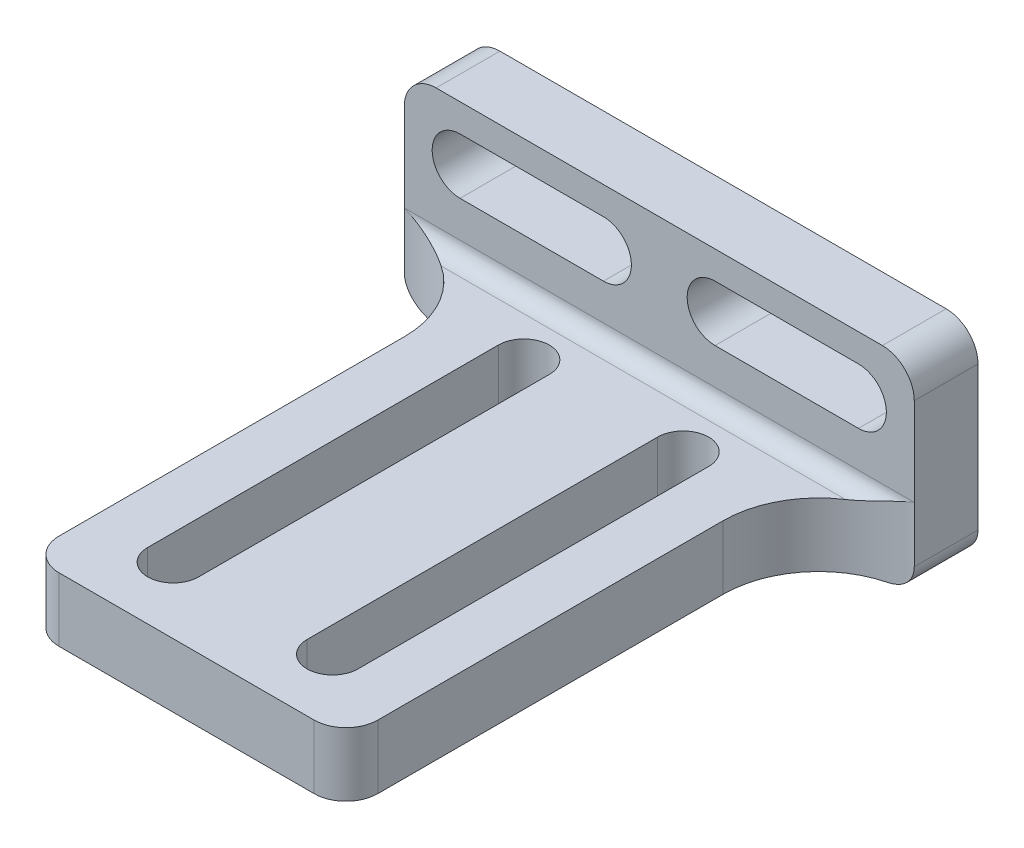
SolidWorks part; units mm, degrees
ref_plane "前视基准面" through (0, 0, 0) normal (0, 0, 1) x (1, 0, 0)
ref_plane "上视基准面" through (0, 0, 0) normal (0, 1, 0) x (1, 0, 0)
ref_plane "右视基准面" through (0, 0, 0) normal (1, 0, 0) x (0, 0, -1)
sketch "草图1" plane through (0, 0, 0) normal (0, 0, 1) x (1, 0, 0)
  line L0 (0, 148.5) -> (0, -94.9538) construction
  line L1 (105, -148.5) -> (-105, -148.5) construction
  line L2 (105, -148.5) -> (105, 148.5) construction
  line L3 (105, 148.5) -> (-105, 148.5) construction
  line L4 (-105, -148.5) -> (-105, 148.5) construction
  line L5 (105, -148.5) -> (-105, 148.5) construction
  line L6 (105, 148.5) -> (-105, -148.5) construction
  line L7 (35.8892, 121.6645) -> (-35.8892, 121.6645)
  line L8 (-35.8892, 121.6645) -> (-66.9017, 102.292)
  line L9 (-75, 40.9339) -> (-75, 31.2613)
  line L10 (-66.9017, 102.292) -> (-66.9017, 52.8701)
  line L11 (75, 40.9339) -> (75, 31.2613)
  line L12 (66.9017, 102.292) -> (66.9017, 52.8701)
  line L13 (35.8892, 121.6645) -> (66.9017, 102.292)
  line L14 (-75, 31.2613) -> (75, 31.2613)
  line L15 (-60, -148.5) -> (-60, -91.8129)
  line L16 (-75, 23.94) -> (75, 23.94)
  line L17 (-75, 23.94) -> (-75, 10.5626)
  line L18 (-38.8455, -105.5906) -> (-66.4608, -113.7617)
  line L19 (-66.4608, -113.7617) -> (-70.1743, -102.7328)
  line L20 (75, 23.94) -> (75, 10.5626)
  line L21 (66.4608, -113.7617) -> (70.1743, -102.7328)
  line L22 (38.8455, -105.5906) -> (66.4608, -113.7617)
  line L23 (-105, 93.0519) -> (105, 93.0519)
  line L24 (-105, 63.0519) -> (105, 63.0519)
  line L25 (-105, -90.0629) -> (-70.5337, -90.0629)
  line L26 (-105, -60.0629) -> (-67.4027, -60.0629)
  line L27 (60, -148.5) -> (60, 148.5)
  line L28 (-60, -58.3129) -> (-45, -58.3129)
  line L29 (-60, -61.8129) -> (-45, -61.8129)
  line L30 (-36, -58.3129) -> (-21, -58.3129)
  line L31 (-36, -61.8129) -> (-21, -61.8129)
  line L32 (-60, -88.3129) -> (-45, -88.3129)
  line L33 (-60, -91.8129) -> (-45, -91.8129)
  line L34 (-36, -88.3129) -> (-21, -88.3129)
  line L35 (-36, -91.8129) -> (-21, -91.8129)
  line L36 (-60, -58.3129) -> (-60, 148.5)
  line L37 (-19.25, -90.0629) -> (105, -90.0629)
  line L38 (-19.25, -60.0629) -> (19.25, -60.0629)
  line L39 (-60, -88.3129) -> (-60, -61.8129)
  line L40 (21, -58.3129) -> (36, -58.3129)
  line L41 (45, -58.3129) -> (60, -58.3129)
  line L42 (60, -61.8129) -> (45, -61.8129)
  line L43 (36, -61.8129) -> (21, -61.8129)
  line L44 (21, -88.3129) -> (36, -88.3129)
  line L45 (21, -91.8129) -> (36, -91.8129)
  line L46 (45, -88.3129) -> (60, -88.3129)
  line L47 (45, -91.8129) -> (60, -91.8129)
  line L48 (37.75, -60.0629) -> (43.25, -60.0629)
  line L49 (58.25, -60.0629) -> (105, -60.0629)
  line L50 (-60, 94.8019) -> (-45, 94.8019)
  line L51 (-36, 94.8019) -> (-21, 94.8019)
  line L52 (-60, 91.3019) -> (-45, 91.3019)
  line L53 (-36, 91.3019) -> (-21, 91.3019)
  line L54 (-60, 64.8019) -> (-45, 64.8019)
  line L55 (-60, 61.3019) -> (-45, 61.3019)
  line L56 (-36, 64.8019) -> (-21, 64.8019)
  line L57 (-36, 61.3019) -> (-21, 61.3019)
  line L58 (21, 94.8019) -> (36, 94.8019)
  line L59 (21, 91.3019) -> (36, 91.3019)
  line L60 (45, 94.8019) -> (60, 94.8019)
  line L61 (45, 91.3019) -> (60, 91.3019)
  line L62 (21, 61.3019) -> (36, 61.3019)
  line L63 (21, 64.8019) -> (36, 64.8019)
  line L64 (45, 61.3019) -> (60, 61.3019)
  line L65 (45, 64.8019) -> (60, 64.8019)
  line L66 (-33.1709, -104.7687) -> (33.1709, -104.7687)
  line L67 (0, -104.7687) -> (0, -148.5) construction
  arc A0 (-75, 40.9339) -> (-66.9017, 52.8701) centre (-79.7474, 52.8701) ccw
  arc A1 (75, 40.9339) -> (66.9017, 52.8701) centre (79.7474, 52.8701) cw
  arc A3 (-60, -88.3129) -> (-60, -91.8129) centre (-60, -90.0629) ccw
  arc A4 (-60, -58.3129) -> (-60, -61.8129) centre (-60, -60.0629) ccw
  circle A5 centre (-60, 63.0519) radius 1.75
  circle A6 centre (-60, 93.0519) radius 1.75
  circle A7 centre (60, 93.0519) radius 1.75
  circle A8 centre (60, 63.0519) radius 1.75
  arc A9 (60, -91.8129) -> (60, -88.3129) centre (60, -90.0629) ccw
  arc A10 (60, -61.8129) -> (60, -58.3129) centre (60, -60.0629) ccw
  arc A11 (-36, -58.3129) -> (-36, -61.8129) centre (-36, -60.0629) ccw
  arc A12 (-36, -88.3129) -> (-36, -91.8129) centre (-36, -90.0629) ccw
  arc A13 (36, -61.8129) -> (36, -58.3129) centre (36, -60.0629) ccw
  arc A14 (36, -91.8129) -> (36, -88.3129) centre (36, -90.0629) ccw
  arc A15 (-45, -61.8129) -> (-45, -58.3129) centre (-45, -60.0629) ccw
  arc A16 (-21, -61.8129) -> (-21, -58.3129) centre (-21, -60.0629) ccw
  arc A17 (-45, -91.8129) -> (-45, -88.3129) centre (-45, -90.0629) ccw
  arc A18 (-21, -91.8129) -> (-21, -88.3129) centre (-21, -90.0629) ccw
  arc A19 (45, -58.3129) -> (45, -61.8129) centre (45, -60.0629) ccw
  arc A20 (21, -58.3129) -> (21, -61.8129) centre (21, -60.0629) ccw
  arc A21 (21, -88.3129) -> (21, -91.8129) centre (21, -90.0629) ccw
  arc A22 (45, -88.3129) -> (45, -91.8129) centre (45, -90.0629) ccw
  circle A23 centre (-36, 93.0519) radius 1.75
  circle A24 centre (-36, 63.0519) radius 1.75
  circle A25 centre (36, 93.0519) radius 1.75
  circle A26 centre (36, 63.0519) radius 1.75
  circle A27 centre (-45, 93.0519) radius 1.75
  circle A28 centre (-21, 93.0519) radius 1.75
  circle A29 centre (-45, 63.0519) radius 1.75
  circle A30 centre (-21, 63.0519) radius 1.75
  circle A31 centre (21, 93.0519) radius 1.75
  circle A32 centre (21, 63.0519) radius 1.75
  circle A33 centre (45, 93.0519) radius 1.75
  circle A34 centre (45, 63.0519) radius 1.75
  arc A35 (33.1709, -104.7687) -> (38.8455, -105.5906) centre (33.1709, -124.7687) cw
  arc A36 (-33.1709, -104.7687) -> (-38.8455, -105.5906) centre (-33.1709, -124.7687) ccw
  spline S0 degree 3 poles (-75, 10.5626) (-72.6959, 1.9073) (-70.3396, -13.3728) (-67.1028, -43.6255) (-66.7657, -72.9327) (-71.8903, -95.1489) (-70.1743, -102.7328) knots 0 0 0 0 0.235247 0.406294 0.801186 1 1 1 1
  spline S1 degree 3 poles (75, 10.5626) (72.6959, 1.9073) (70.3396, -13.3728) (67.1028, -43.6255) (66.7657, -72.9327) (71.8903, -95.1489) (70.1743, -102.7328) knots 0 0 0 0 0.235247 0.406294 0.801186 1 1 1 1
  point P0 (0, 0)
  point P27 (0, 121.6645)
  point P42 (0, -94.0966)
  dimension "D1" = 60
  dimension "D4" = 20
  dimension "D5" = 24
  dimension "D7" = 24
  dimension "D9" = 15
  dimension "D10" = 15
  dimension "D13" = 24
  dimension "D17" = 15
  dimension "D2" = 30
  dimension "D3" = 30
  dimension "D6" = 24
  dimension "D8" = 24
  dimension "D11" = 15
  dimension "D12" = 15
  dimension "D14" = 24
  dimension "D15" = 24
  dimension "D16" = 24
  dimension "D18" = 15
  dimension "D19" = 15
  dimension "D20" = 15
  dimension "D21" = 15
  dimension "D22" = 15
  dimension "D23" = 15
  dimension "D24" = 15
  dimension "D25" = 15
  dimension "D26" = 15
  dimension "D27" = 15
  dimension "D28" = 15
  dimension "D29" = 3.5
  dimension "D30" = 3.5
  dimension "D31" = 3.5
extrude "凸台-拉伸1" add sketch "草图1" along normal blind 3 contours A34 L24 A26 L62 A32 A30 L57 A24 A29 L55 L36 L14 L27 L64 | A5 L24 L10 A0 L9 L14 L36 | A6 L23 L10 L24 A5 L36 | A6 L36 L8 L10 L23 | A33 L60 L27 L13 L7 L8 L36 L50 A27 L23 A23 L51 A28 A31 L58 A25 | A34 L65 L27 L61 A33 L23 A25 L59 A31 A28 L53 A23 A27 L52 L36 L54 A29 L24 A24 L56 A30 A32 L63 A26 | A7 L23 L12 L13 L27 | A8 L24 L12 L23 A7 L27 | A8 L27 L14 L11 A1 L12 L24 | A22 L46 L27 L42 A19 A13 L43 A20 A16 L31 A11 L30 L40 L41 L16 L36 L28 A15 L29 L39 L32 A17 L33 L15 L18 L22 L47 A14 L45 A21 A18 L35 A12 L34 | L17 S0 L19 L18 L15 A3 L39 A4 L36 L16 | S1 L20 L16 L27 A10 L49 | S1 L49 A10 L27 A9 L37 | S1 L37 A9 L27 L22 L21 region at (0, 106.7597, 0) region at (63.3118, 98.9762, 0) region at (-63.3118, 98.9762, 0) region at (63.5153, 78.0519, 0) region at (-63.5153, 78.0519, 0) region at (65.7633, 44.067, 0) region at (0, 78.0519, 0) region at (-65.7633, 44.067, 0) region at (0, 46.6707, 0) region at (0, -40.0712, 0) region at (65.6849, -11.6712, 0) region at (-65.3451, -38.0027, 0) region at (64.4303, -76.0355, 0) region at (65.0264, -100.7629, 0)
sketch "草图7" plane through (0, 0, 0) normal (0, 0, -1) x (-1, 0, 0)
  line L0 (0, 121.6645) -> (0, -104.7687) construction
  line L1 (-35.8892, 121.6645) -> (35.8892, 121.6645) construction
  line L2 (33.1709, -104.7687) -> (-33.1709, -104.7687) construction
  line L3 (0, 41.2613) -> (-21, 41.2613) construction
  line L4 (0, 41.2613) -> (21, 41.2613) construction
  line L5 (0, 13.94) -> (-21, 13.94) construction
  line L6 (0, 13.94) -> (21, 13.94) construction
  line L7 (75, 23.94) -> (-75, 23.94) construction
  line L8 (75, 31.2613) -> (-75, 31.2613) construction
  circle A0 centre (-21, 41.2613) radius 2.25
  circle A1 centre (21, 41.2613) radius 2.25
  circle A2 centre (-21, 13.94) radius 2.25
  circle A3 centre (21, 13.94) radius 2.25
  dimension "D1" = 10
  dimension "D2" = 10
extrude "切除-拉伸2" cut sketch "草图7" against normal through all
sketch "草图8" plane through (0, 0, 3) normal (0, 0, 1) x (1, 0, 0)
  line L0 (0, 121.6645) -> (0, -1.9696) construction
  line L1 (35.8892, 121.6645) -> (-35.8892, 121.6645) construction
  line L2 (-33.1709, -104.7687) -> (33.1709, -104.7687) construction
  line L3 (-33.409, 20.409) -> (-12.6214, -0.3786)
  line L4 (31.818, -51.182) -> (-31.818, -51.182)
  line L5 (35, -48) -> (35, 15.6418)
  line L8 (-35, 18.818) -> (-12.6214, -3.5605) construction
  line L9 (-33.409, -52.773) -> (-12.5737, -31.9377)
  line L10 (-36.591, 17.227) -> (-15.8034, -3.5605)
  line L11 (33.4105, 20.4105) -> (12.573, -0.427)
  line L12 (15.803, -3.5609) -> (36.5881, 17.2241)
  line L13 (31.8195, 18.8195) -> (-31.818, 18.818)
  line L14 (-15.8038, -28.8038) -> (-36.591, -49.591)
  line L15 (12.5534, -31.9174) -> (33.409, -52.773)
  line L16 (34.9993, 18.8173) -> (12.6207, -3.5613) construction
  line L17 (0, -30.3951) -> (0, -104.7687) construction
  line L18 (-35, -48) -> (-35, 15.636)
  line L19 (-11.9624, -1.9696) -> (-14.2124, -1.9696) construction
  line L20 (15.8034, -28.8034) -> (36.591, -49.591)
  line L21 (14.2117, -30.3951) -> (11.9607, -30.3951) construction
  line L22 (14.2117, -30.3951) -> (14.2117, -28.1441) construction
  line L23 (14.2117, -1.9696) -> (11.9612, -1.9696) construction
  line L24 (-14.2124, -30.3951) -> (-14.2124, -28.1446) construction
  line L25 (14.2117, -30.3951) -> (12.62, -28.8034) construction
  line L26 (14.2117, -1.9696) -> (12.6204, -3.5609) construction
  line L27 (12.6207, -28.8027) -> (35, -51.182) construction
  line L28 (-12.6215, -3.5606) -> (-14.2124, -1.9696) construction
  line L29 (-14.2124, -4.2196) -> (-14.2124, -1.9696) construction
  line L30 (-12.6214, -28.8034) -> (-35, -51.182) construction
  line L31 (-12.6211, -28.8037) -> (-14.2124, -30.3951) construction
  line L32 (-11.9619, -30.3951) -> (-14.2124, -30.3951) construction
  line L33 (14.2117, -4.2201) -> (14.2117, -1.9696) construction
  line L34 (11.0312, -30.3951) -> (0, -30.3951) construction
  arc A0 (-33.409, 20.409) -> (-36.591, 17.227) centre (-35, 18.818) ccw
  arc A1 (36.5881, 17.2241) -> (33.4105, 20.4105) centre (34.9993, 18.8173) ccw
  arc A2 (-36.591, -49.591) -> (-33.409, -52.773) centre (-35, -51.182) ccw
  arc A3 (33.409, -52.773) -> (36.591, -49.591) centre (35, -51.182) ccw
  arc A4 (-15.8034, -3.5605) -> (-12.6214, -0.3786) centre (-14.2124, -1.9696) ccw
  arc A5 (12.6692, -0.3308) -> (15.803, -3.5609) centre (14.2117, -1.9696) ccw
  arc A6 (-12.6699, -32.0338) -> (-15.8038, -28.8038) centre (-14.2124, -30.3951) ccw
  arc A7 (15.8034, -28.8034) -> (12.6894, -32.0534) centre (14.2117, -30.3951) ccw
  circle A8 centre (-0.0004, -16.1823) radius 8
  point P6 (0, -16.182)
  point P13 (-0.0004, -16.1823)
extrude "切除-拉伸3" cut sketch "草图8" against normal through all contours L10 A4 L3 A0 | L11 A5 L12 A1 | L20 A7 L15 A3 | L9 A6 L14 A2 | A8 region at (-24.6062, 8.4242, 3) region at (24.6054, 8.4234, 3) region at (-24.6061, -40.7881, 3) region at (24.6056, -40.7877, 3) region at (-0.0004, -16.1823, 3)
sketch "草图9" plane through (0, 0, 3) normal (0, 0, 1) x (1, 0, 0)
  line L0 (-70.7828, -98.747) -> (70.7828, -98.747) construction
  line L1 (0, -98.747) -> (0, -104.7687) construction
  line L2 (55, -100.497) -> (20, -100.497)
  line L3 (-55, -96.997) -> (-20, -96.997)
  line L4 (-55, -100.497) -> (-20, -100.497)
  line L5 (-33.1709, -104.7687) -> (33.1709, -104.7687) construction
  line L6 (55, -96.997) -> (20, -96.997)
  arc A0 (-55, -96.997) -> (-55, -100.497) centre (-55, -98.747) ccw
  arc A1 (-20, -100.497) -> (-20, -96.997) centre (-20, -98.747) ccw
  arc A2 (20, -100.497) -> (20, -96.997) centre (20, -98.747) cw
  arc A3 (55, -96.997) -> (55, -100.497) centre (55, -98.747) cw
  spline S0 degree 3 poles (-75, 10.5626) (-72.6959, 1.9073) (-70.3396, -13.3728) (-67.1028, -43.6255) (-66.7657, -72.9327) (-71.8903, -95.1489) (-70.1743, -102.7328) knots 0 0 0 0 0.235247 0.406294 0.801186 1 1 1 1 construction
  spline S1 degree 3 poles (75, 10.5626) (72.6959, 1.9073) (70.3396, -13.3728) (67.1028, -43.6255) (66.7657, -72.9327) (71.8903, -95.1489) (70.1743, -102.7328) knots 0 0 0 0 0.235247 0.406294 0.801186 1 1 1 1 construction
  dimension "D1" = 35
  dimension "D2" = 20
extrude "切除-拉伸4" cut sketch "草图9" against normal blind 3
sketch "草图10" plane through (0, 0, 3) normal (0, 0, 1) x (1, 0, 0)
  line L0 (-21, -60.0629) -> (-21, -90.0629) construction
  line L1 (21, -60.0629) -> (21, -90.0629) construction
  line L2 (-21, -75.0629) -> (-17.5, -75.0629) construction
  line L4 (12.5, -80.0629) -> (-12.5, -80.0629)
  line L6 (12.5, -70.0629) -> (-12.5, -70.0629)
  line L11 (17.5, -75.0629) -> (21, -75.0629) construction
  arc A0 (-12.5, -70.0629) -> (-12.5, -80.0629) centre (-12.5, -75.0629) ccw
  arc A1 (12.5, -80.0629) -> (12.5, -70.0629) centre (12.5, -75.0629) ccw
  point P11 (0, -75.0629)
extrude "切除-拉伸5" cut sketch "草图10" against normal blind 3
sketch "草图11" plane through (0, 0, 3) normal (0, 0, 1) x (1, 0, 0)
  line L0 (-21, 93.0519) -> (-21, 63.0519) construction
  line L1 (21, 93.0519) -> (21, 63.0519) construction
  line L2 (-21, 78.0519) -> (-20, 78.0519) construction
  line L4 (15, 73.0519) -> (-15, 73.0519)
  line L6 (15, 83.0519) -> (-15, 83.0519)
  line L10 (20, 78.0519) -> (21, 78.0519) construction
  arc A0 (-15, 83.0519) -> (-15, 73.0519) centre (-15, 78.0519) ccw
  arc A1 (15, 73.0519) -> (15, 83.0519) centre (15, 78.0519) ccw
  point P10 (0, 78.0519)
  dimension "D1" = 30
extrude "切除-拉伸8" cut sketch "草图11" against normal blind 3
sketch "草图12" plane through (0, 0, 3) normal (0, 0, 1) x (1, 0, 0)
  line L0 (0, 121.6645) -> (0, 83.0519) construction
  line L1 (35.8892, 121.6645) -> (-35.8892, 121.6645) construction
  line L2 (15, 83.0519) -> (-15, 83.0519) construction
  circle A0 centre (0, 106.3718) radius 11 construction
  circle A1 centre (0, 106.3718) radius 8 construction
  circle A2 centre (0, 114.3718) radius 1.7
  circle A3 centre (0, 98.3718) radius 1.7
  circle A4 centre (8, 106.3718) radius 1.7
  circle A5 centre (-8, 106.3718) radius 1.7
extrude "切除-拉伸9" cut sketch "草图12" against normal blind 3
sketch "草图13" plane through (0, 0, 3) normal (0, 0, 1) x (1, 0, 0)
  line L0 (0, -104.7687) -> (0, -80.0629) construction
  line L1 (-33.1709, -104.7687) -> (33.1709, -104.7687) construction
  line L2 (-12.5, -80.0629) -> (12.5, -80.0629) construction
  circle A0 centre (0, -92.4158) radius 8 construction
  circle A1 centre (0, -84.4158) radius 1.7
  circle A2 centre (8, -92.4158) radius 1.7
  circle A3 centre (0, -100.4158) radius 1.7
  circle A4 centre (-8, -92.4158) radius 1.7
extrude "切除-拉伸11" cut sketch "草图13" against normal blind 3
sketch "草图14" plane through (0, 0, 3) normal (0, 0, 1) x (1, 0, 0)
  line L0 (0, 23.94) -> (0, -104.7687) construction
  line L1 (-55.4755, 8.9197) -> (-55.4755, -46.0803)
  line L2 (-58.9755, 8.9197) -> (-58.9755, -46.0803)
  line L3 (-75, 23.94) -> (75, 23.94) construction
  line L4 (-33.1709, -104.7687) -> (33.1709, -104.7687) construction
  line L5 (58.9755, 8.9197) -> (58.9755, -46.0803)
  line L6 (55.4755, 8.9197) -> (55.4755, -46.0803)
  arc A0 (-55.4755, 8.9197) -> (-58.9755, 8.9197) centre (-57.2255, 8.9197) ccw
  arc A1 (-58.9755, -46.0803) -> (-55.4755, -46.0803) centre (-57.2255, -46.0803) ccw
  arc A2 (58.9755, -46.0803) -> (55.4755, -46.0803) centre (57.2255, -46.0803) cw
  arc A3 (55.4755, 8.9197) -> (58.9755, 8.9197) centre (57.2255, 8.9197) cw
extrude "切除-拉伸12" cut sketch "草图14" against normal through all
fillet "圆角1" radius 2 2 edges at (75, 31.2613, 1.5) (-75, 31.2613, 1.5)
fillet "圆角2" radius 2 2 edges at (-75, 23.94, 1.5) (75, 23.94, 1.5)
sketch "草图15" plane through (0, 0, 0) normal (0, 0, -1) x (-1, 0, 0)
  line L0 (0, 121.6645) -> (0, 31.2613) construction
  line L1 (-35.8892, 121.6645) -> (35.8892, 121.6645) construction
  line L2 (73, 31.2613) -> (-73, 31.2613) construction
  line L3 (-27.5188, 121.6645) -> (-63.6963, 99.0657) construction
  line L4 (-35.8892, 121.6645) -> (-66.9017, 102.292) construction
  line L5 (-61.1842, 102.4035) -> (-34.7748, 118.9006)
  line L6 (-59.5948, 99.8591) -> (-33.1854, 116.3562)
  line L7 (27.5188, 121.6645) -> (63.6963, 99.0657) construction
  line L8 (59.5948, 99.8591) -> (33.1854, 116.3562)
  line L9 (61.1842, 102.4035) -> (34.7748, 118.9006)
  arc A0 (-61.1842, 102.4035) -> (-59.5948, 99.8591) centre (-60.3895, 101.1313) ccw
  arc A1 (-33.1854, 116.3562) -> (-34.7748, 118.9006) centre (-33.9801, 117.6284) ccw
  arc A2 (33.1854, 116.3562) -> (34.7748, 118.9006) centre (33.9801, 117.6284) cw
  arc A3 (61.1842, 102.4035) -> (59.5948, 99.8591) centre (60.3895, 101.1313) cw
extrude "切除-拉伸13" cut sketch "草图15" against normal through all
sketch "草图16" plane through (0, 0, 0) normal (0, 0, -1) x (-1, 0, 0)
  line L0 (0, 121.6645) -> (0, 31.2613) construction
  line L1 (-35.8892, 121.6645) -> (35.8892, 121.6645) construction
  line L2 (73, 31.2613) -> (-73, 31.2613) construction
  line L3 (-21, 41.2613) -> (-66.71, 41.2613) construction
  line L4 (-61.517, 42.7613) -> (-32.0563, 42.7613)
  line L5 (-61.517, 39.7613) -> (-32.0563, 39.7613)
  line L6 (21, 41.2613) -> (66.71, 41.2613) construction
  line L7 (61.517, 39.7613) -> (32.0563, 39.7613)
  line L8 (61.517, 42.7613) -> (32.0563, 42.7613)
  arc A0 (-61.517, 42.7613) -> (-61.517, 39.7613) centre (-61.517, 41.2613) ccw
  arc A1 (-32.0563, 39.7613) -> (-32.0563, 42.7613) centre (-32.0563, 41.2613) ccw
  arc A2 (32.0563, 39.7613) -> (32.0563, 42.7613) centre (32.0563, 41.2613) cw
  arc A3 (61.517, 42.7613) -> (61.517, 39.7613) centre (61.517, 41.2613) cw
extrude "切除-拉伸14" cut sketch "草图16" against normal through all
sketch "草图17" plane through (0, 0, 0) normal (0, 0, -1) x (-1, 0, 0)
  text T0 "Y" font "黑体" height in points 72
extrude "切除-拉伸15" cut sketch "草图17" against normal through all
sketch "草图18" plane through (0, 0, 0) normal (0, 0, -1) x (-1, 0, 0)
  text T0 "H" font "黑体" height in points 72
extrude "切除-拉伸16" cut sketch "草图18" against normal through all
ref_plane "基准面1" through (0, 0, 13) normal (0, 0, 1) x (1, 0, 0)
sketch "草图19" plane through (0, 0, 13) normal (0, 0, 1) x (1, 0, 0)
  line L2 (20, -100.497) -> (55, -100.497) construction
  line L3 (55, -96.997) -> (20, -96.997) construction
  line L6 (20, -100.497) -> (45, -100.497)
  line L7 (45, -96.997) -> (20, -96.997)
  line L8 (0, -100.4158) -> (0, -70.0629) construction
  line L9 (12.5, -70.0629) -> (-12.5, -70.0629) construction
  line L10 (45, -98.747) -> (20, -98.747) construction
  line L11 (-16.5, -96.247) -> (-43.7, -100.497) construction
  line L12 (16.5, -101.247) -> (16.5, -104.7687) construction
  line L14 (16.5, -101.247) -> (16.5, -96.247)
  line L15 (16.5, -96.247) -> (48.5, -96.247)
  line L16 (48.5, -101.247) -> (48.5, -96.247)
  line L17 (16.5, -101.247) -> (48.5, -96.247) construction
  line L18 (16.5, -96.247) -> (43.7, -100.497) construction
  line L19 (-33.1709, -104.7687) -> (33.1709, -104.7687) construction
  line L21 (48.5, -101.247) -> (48.5, -104.7687)
  line L22 (48.5, -104.7687) -> (16.5, -104.7687)
  line L23 (16.5, -101.247) -> (16.5, -104.7687)
  line L24 (-16.5, -101.247) -> (-48.5, -96.247) construction
  line L25 (-16.5, -101.247) -> (-16.5, -104.7687) construction
  line L26 (-45, -98.747) -> (-20, -98.747) construction
  line L27 (-16.5, -101.247) -> (-16.5, -104.7687)
  line L28 (-48.5, -104.7687) -> (-16.5, -104.7687)
  line L29 (-48.5, -101.247) -> (-48.5, -104.7687)
  line L30 (-48.5, -101.247) -> (-48.5, -96.247)
  line L31 (-16.5, -96.247) -> (-48.5, -96.247)
  line L32 (-16.5, -101.247) -> (-16.5, -96.247)
  line L33 (-45, -96.997) -> (-20, -96.997)
  line L34 (-20, -100.497) -> (-45, -100.497)
  arc A0 (-45, -100.497) -> (-45, -96.997) centre (-45, -98.747) cw
  arc A2 (20, -96.997) -> (20, -100.497) centre (20, -98.747) ccw construction
  arc A3 (-20, -96.997) -> (-20, -100.497) centre (-20, -98.747) cw
  arc A6 (20, -96.997) -> (20, -100.497) centre (20, -98.747) ccw
  arc A8 (45, -100.497) -> (45, -96.997) centre (45, -98.747) ccw
  point P2 (32.5, -98.747)
  point P36 (-32.5, -98.747)
extrude "凸台-拉伸2" add sketch "草图19" along normal blind 4 separate body
sketch "草图21" plane through (0, 0, 17) normal (0, 0, 1) x (1, 0, 0)
  line L0 (-46.75, -98.747) -> (-18.25, -98.747) construction
  line L1 (-32.5, -96.997) -> (-32.5, -100.497) construction
  line L2 (-20, -96.997) -> (-45, -96.997) construction
  line L3 (-45, -100.497) -> (-20, -100.497) construction
  line L4 (-36, -96.997) -> (-29, -96.997)
  line L5 (-36, -100.497) -> (-29, -100.497)
  line L6 (0, -104.7687) -> (0, -70.0629) construction
  line L7 (-33.1709, -104.7687) -> (33.1709, -104.7687) construction
  line L8 (12.5, -70.0629) -> (-12.5, -70.0629) construction
  line L9 (32.5, -96.997) -> (32.5, -100.497) construction
  line L10 (36, -100.497) -> (29, -100.497)
  line L11 (36, -96.997) -> (29, -96.997)
  arc A0 (-45, -96.997) -> (-45, -100.497) centre (-45, -98.747) ccw construction
  arc A1 (-20, -100.497) -> (-20, -96.997) centre (-20, -98.747) ccw construction
  arc A2 (-36, -100.497) -> (-36, -96.997) centre (-36, -98.747) ccw
  arc A3 (-29, -96.997) -> (-29, -100.497) centre (-29, -98.747) ccw
  arc A4 (29, -96.997) -> (29, -100.497) centre (29, -98.747) cw
  arc A5 (36, -100.497) -> (36, -96.997) centre (36, -98.747) cw
  point P18 (-32.5, -98.747)
  dimension "D1" = 3.5
  dimension "D2" = 3.5
extrude "凸台-拉伸4" add sketch "草图21" against normal up to surface (4 mm away) up to face at (32.5, -100.5079, 13)
sketch "草图23" plane through (0, 0, 13) normal (0, 0, 1) x (1, 0, 0)
  line L0 (-16.5, -104.7687) -> (-16.5, -120.6552) construction
  line L1 (48.5, -104.7687) -> (48.5, -120.6552) construction
  line L2 (-16.5, -104.7687) -> (-16.5, -96.247) construction
  line L4 (-48.5, -104.7687) -> (-48.5, -107.7687)
  line L5 (-48.5, -107.7687) -> (-16.5, -107.7687)
  line L6 (-16.5, -104.7687) -> (-16.5, -107.7687)
  line L8 (16.5, -104.7687) -> (16.5, -107.7687)
  line L9 (16.5, -107.7687) -> (48.5, -107.7687)
  line L10 (48.5, -104.7687) -> (48.5, -107.7687)
  line L12 (-48.5, -104.7687) -> (-48.5, -102.7687)
  line L13 (-48.5, -102.7687) -> (-16.5, -102.7687)
  line L14 (-16.5, -104.7687) -> (-16.5, -102.7687)
  line L17 (16.5, -104.7687) -> (16.5, -102.7687)
  line L18 (16.5, -102.7687) -> (48.5, -102.7687)
  line L19 (48.5, -104.7687) -> (48.5, -102.7687)
extrude "凸台-拉伸5" add sketch "草图23" along normal blind 35
sketch "草图25" plane through (0, -102.7687, 0) normal (0, 1, 0) x (1, 0, 0)
  line L0 (-32.5, -17) -> (-32.5, -48) construction
  line L1 (-16.5, -17) -> (-48.5, -17) construction
  line L2 (-16.5, -48) -> (-48.5, -48) construction
  line L3 (-22.5, -17) -> (-22.5, -48)
  line L4 (-48.5, -17) -> (-42.5, -17)
  line L5 (-48.5, -17) -> (-48.5, -48)
  line L6 (-48.5, -48) -> (-42.5, -48)
  line L7 (-42.5, -17) -> (-42.5, -48)
  line L8 (-16.5, -17) -> (-16.5, -48)
  line L9 (-16.5, -17) -> (-22.5, -17)
  line L10 (-16.5, -48) -> (-22.5, -48)
  line L11 (0, 0) -> (0, -48) construction
  line L12 (32.5, -17) -> (32.5, -48) construction
  line L13 (16.5, -48) -> (22.5, -48)
  line L14 (16.5, -17) -> (22.5, -17)
  line L15 (16.5, -17) -> (16.5, -48)
  line L16 (42.5, -17) -> (42.5, -48)
  line L17 (48.5, -48) -> (42.5, -48)
  line L18 (48.5, -17) -> (48.5, -48)
  line L19 (48.5, -17) -> (42.5, -17)
  line L20 (22.5, -17) -> (22.5, -48)
extrude "切除-拉伸17" cut sketch "草图25" against normal up to surface (5 mm away) up to face at (-32.5, -107.7687, 30.5)
fillet "圆角3" radius 6 2 edges at (22.5, -105.2687, 17) (42.5, -105.2687, 17)
fillet "圆角4" radius 6 2 edges at (-42.5, -105.2687, 17) (-22.5, -105.2687, 17)
fillet "圆角5" radius 1.5 4 edges at (48.5, -107.7687, 15) (16.5, -107.7687, 15) (16.5, -96.247, 15) (48.5, -96.247, 15)
fillet "圆角6" radius 1.5 4 edges at (-48.5, -107.7687, 15) (-48.5, -96.247, 15) (-16.5, -96.247, 15) (-16.5, -107.7687, 15)
sketch "草图26" plane through (0, -107.7687, 0) normal (0, -1, 0) x (1, 0, 0)
  line L0 (0, 0) -> (0, 51.2514) construction
  line L2 (22.5, 48) -> (42.5, 48) construction
  line L4 (42.5, 48) -> (32.5, 48) construction
  line L6 (75.7359, 13) -> (-75.7359, 13) construction
  line L7 (37.5, 20.5) -> (37.5, 13) construction
  line L9 (35.9, 20.5) -> (35.9, 32.5)
  line L11 (39.1, 20.5) -> (39.1, 32.5)
  line L12 (27.5, 30.9) -> (27.5, 22.1) construction
  line L13 (25.9, 20.5) -> (25.9, 32.5)
  line L14 (37.5, 30.9) -> (37.5, 22.1) construction
  line L15 (29.1, 20.5) -> (29.1, 32.5)
  line L16 (-37.5, 34.1) -> (-37.5, 22.1) construction
  line L17 (-27.5, 34.1) -> (-27.5, 22.1) construction
  line L18 (-29.1, 20.5) -> (-29.1, 32.5)
  line L19 (-25.9, 20.5) -> (-25.9, 32.5)
  line L20 (-39.1, 20.5) -> (-39.1, 32.5)
  line L21 (-35.9, 20.5) -> (-35.9, 32.5)
  arc A1 (35.9, 20.5) -> (39.1, 20.5) centre (37.5, 20.5) ccw
  arc A2 (29.1, 20.5) -> (25.9, 20.5) centre (27.5, 20.5) cw
  arc A5 (-29.1, 20.5) -> (-25.9, 20.5) centre (-27.5, 20.5) ccw
  arc A6 (-35.9, 20.5) -> (-39.1, 20.5) centre (-37.5, 20.5) cw
  arc A8 (39.1, 32.5) -> (35.9, 32.5) centre (37.5, 32.5) ccw
  arc A9 (29.1, 32.5) -> (25.9, 32.5) centre (27.5, 32.5) ccw
  arc A10 (-29.1, 32.5) -> (-25.9, 32.5) centre (-27.5, 32.5) cw
  arc A11 (-39.1, 32.5) -> (-35.9, 32.5) centre (-37.5, 32.5) cw
  point P15 (37.5, 30.5)
  point P32 (27.5, 30.5)
  point P49 (-27.5, 30.5)
  point P50 (-37.5, 30.5)
  dimension "D1" = 12
extrude "切除-拉伸18" cut sketch "草图26" against normal blind 5
sketch "草图27" plane through (42.5, 0, 0) normal (1, 0, 0) x (0, 0, -1)
  line L0 (-17, -106.2687) -> (-17, -102.7687) construction
  line L1 (-48, -102.7687) -> (-17, -102.7687)
  line L2 (-48, -102.7687) -> (-48, -103.7687)
  line L3 (-48, -103.7687) -> (-17, -103.7687)
  line L4 (-17, -102.7687) -> (-17, -103.7687)
extrude "切除-拉伸19" cut sketch "草图27" against normal blind 95 and the other way blind 15
fillet "圆角8" radius 1 1 edges at (-32.5, -103.7687, 17)
fillet "圆角9" radius 1 1 edges at (32.5, -103.7687, 17)
fillet "圆角10" radius 3 2 edges at (-22.5, -105.7687, 48) (-42.5, -105.7687, 48)
sketch "草图28" plane through (0, -107.7687, 0) normal (0, -1, 0) x (1, 0, 0)
  line L0 (-42.5, 23) -> (-42.5, 45) construction
  line L1 (42.5, 48) -> (-42.5, 48)
  line L2 (42.5, 48) -> (42.5, 37.6569)
  line L3 (42.5, 37.6569) -> (-42.5, 37.6569)
  line L4 (-42.5, 48) -> (-42.5, 37.6569)
extrude "切除-拉伸20" cut sketch "草图28" against normal blind 5
fillet "圆角12" radius 3 2 edges at (22.5, -105.7687, 37.6569) (42.5, -105.7687, 37.6569)
fillet "圆角13" radius 3 2 edges at (-42.5, -105.7687, 37.6569) (-22.5, -105.7687, 37.6569)
ref_plane "基准面2" through (0, -112.7687, 0) normal (0, -1, 0) x (-1, 0, 0)
sketch "草图31" plane through (0, 121.6645, 0) normal (0, 1, 0) x (1, 0, 0)
  line L1 (-79.0565, 2.2725) -> (80.5534, 2.2725)
  line L2 (-79.0565, 2.2725) -> (-79.0565, -7.1241)
  line L3 (-79.0565, -7.1241) -> (80.5534, -7.1241)
  line L4 (80.5534, 2.2725) -> (80.5534, -7.1241)
extrude "切除-拉伸21" cut sketch "草图31" against normal blind 265
sketch "草图32" plane through (0, 0, 13) normal (0, 0, -1) x (-1, 0, 0)
  line L0 (-16.5, -102.0079) -> (-16.5, -88.4862) construction
  line L1 (-16.5, -97.747) -> (-16.5, -106.2687) construction
  line L2 (48.5, -102.0079) -> (48.5, -85.1941) construction
  line L3 (48.5, -97.747) -> (48.5, -106.2687) construction
  line L4 (-48.5, -97.747) -> (-48.5, -87.7348) construction
  line L5 (16.5, -97.747) -> (16.5, -85.1941) construction
  line L6 (-29, -96.997) -> (-20, -96.997) construction
  line L7 (-48.5, -97.747) -> (-46.4361, -97.747)
  line L8 (-48.5, -97.747) -> (-48.5, -95.247)
  line L9 (-48.5, -95.247) -> (-16.5, -95.247)
  line L10 (-16.5, -97.747) -> (-16.5, -95.247)
  line L11 (-45, -96.997) -> (-36, -96.997) construction
  line L12 (-29, -96.997) -> (-20, -96.997)
  line L13 (-45, -96.997) -> (-36, -96.997)
  line L14 (-34.5639, -97.747) -> (-30.4361, -97.747)
  line L15 (-18.5639, -97.747) -> (-16.5, -97.747)
  line L16 (-16.5, -102.0079) -> (16.5, -102.0079) construction
  line L17 (16.5, -106.2687) -> (16.5, -97.747) construction
  line L18 (0, -102.0079) -> (0, -80.5827) construction
  line L19 (18.5639, -97.747) -> (16.5, -97.747)
  line L20 (34.5639, -97.747) -> (30.4361, -97.747)
  line L21 (45, -96.997) -> (36, -96.997)
  line L22 (29, -96.997) -> (20, -96.997)
  line L23 (16.5, -97.747) -> (16.5, -95.247)
  line L24 (48.5, -95.247) -> (16.5, -95.247)
  line L25 (48.5, -97.747) -> (48.5, -95.247)
  line L26 (48.5, -97.747) -> (46.4361, -97.747)
  arc A0 (-20, -100.497) -> (-20, -96.997) centre (-20, -98.747) ccw construction
  arc A1 (-29, -96.997) -> (-29, -100.497) centre (-29, -98.747) ccw construction
  arc A2 (-36, -100.497) -> (-36, -96.997) centre (-36, -98.747) ccw construction
  arc A3 (-45, -96.997) -> (-45, -100.497) centre (-45, -98.747) ccw construction
  arc A4 (-18.5639, -97.747) -> (-20, -96.997) centre (-20, -98.747) ccw
  arc A5 (-29, -96.997) -> (-30.4361, -97.747) centre (-29, -98.747) ccw
  arc A6 (-34.5639, -97.747) -> (-36, -96.997) centre (-36, -98.747) ccw
  arc A7 (-45, -96.997) -> (-46.4361, -97.747) centre (-45, -98.747) ccw
  arc A8 (45, -96.997) -> (46.4361, -97.747) centre (45, -98.747) cw
  arc A9 (34.5639, -97.747) -> (36, -96.997) centre (36, -98.747) cw
  arc A10 (29, -96.997) -> (30.4361, -97.747) centre (29, -98.747) cw
  arc A11 (18.5639, -97.747) -> (20, -96.997) centre (20, -98.747) cw
extrude "凸台-拉伸7" add sketch "草图32" against normal up to surface (4 mm away) up to face at (24.5, -98.747, 17)
fillet "圆角14" radius 2 2 edges at (16.5, -95.247, 15) (48.5, -95.247, 15)
fillet "圆角15" radius 2 2 edges at (-48.5, -95.247, 15) (-16.5, -95.247, 15)
sketch "草图33" plane through (0, -107.7687, 0) normal (0, -1, 0) x (1, 0, 0)
  line L1 (-55.2516, 44.7105) -> (-8.7348, 44.7105)
  line L2 (-55.2516, 44.7105) -> (-55.2516, 7.7038)
  line L3 (-55.2516, 7.7038) -> (-8.7348, 7.7038)
  line L4 (-8.7348, 44.7105) -> (-8.7348, 7.7038)
extrude "切除-拉伸22" cut sketch "草图33" against normal blind 40
sketch "草图34" plane through (0, -107.7687, 0) normal (0, -1, 0) x (1, 0, 0)
  line L0 (22.5, 34.6569) -> (22.5, 60.4736) construction
  line L2 (42.5, 34.6569) -> (22.5, 34.6569)
  line L3 (42.5, 34.6569) -> (42.5, 46.6569)
  line L4 (42.5, 46.6569) -> (22.5, 46.6569)
  line L5 (22.5, 34.6569) -> (22.5, 46.6569)
extrude "凸台-拉伸8" add sketch "草图34" against normal up to surface (4 mm away) up to face at (32.5, -103.7687, 28.3995)
sketch "草图35" plane through (0, -107.7687, 0) normal (0, -1, 0) x (1, 0, 0)
  line L0 (37.5, 18.9) -> (37.5, 30.9) construction
  line L2 (27.5, 18.9) -> (27.5, 33.5186) construction
  line L3 (39.1, 32.5) -> (39.1, 42.5) construction
  line L4 (35.9, 32.5) -> (35.9, 42.5) construction
  line L5 (29.1, 32.5) -> (29.1, 42.5) construction
  line L6 (25.9, 32.5) -> (25.9, 42.5) construction
  line L7 (39.1, 32.5) -> (39.1, 42.5)
  line L8 (35.9, 32.5) -> (35.9, 42.5)
  line L9 (29.1, 32.5) -> (29.1, 42.5)
  line L10 (25.9, 32.5) -> (25.9, 42.5)
  line L11 (37.5, 34.1) -> (37.5, 44.1) construction
  arc A0 (35.9, 20.5) -> (39.1, 20.5) centre (37.5, 20.5) ccw construction
  arc A1 (25.9, 20.5) -> (29.1, 20.5) centre (27.5, 20.5) ccw construction
  arc A2 (39.1, 42.5) -> (35.9, 42.5) centre (37.5, 42.5) ccw
  arc A3 (29.1, 42.5) -> (25.9, 42.5) centre (27.5, 42.5) ccw
  arc A8 (35.9, 32.5) -> (39.1, 32.5) centre (37.5, 32.5) ccw
  arc A9 (25.9, 32.5) -> (29.1, 32.5) centre (27.5, 32.5) ccw
  dimension "D1" = 10
extrude "切除-拉伸23" cut sketch "草图35" against normal blind 10
fillet "圆角17" radius 2 2 edges at (22.5, -105.7687, 46.6569) (42.5, -105.7687, 46.6569)
